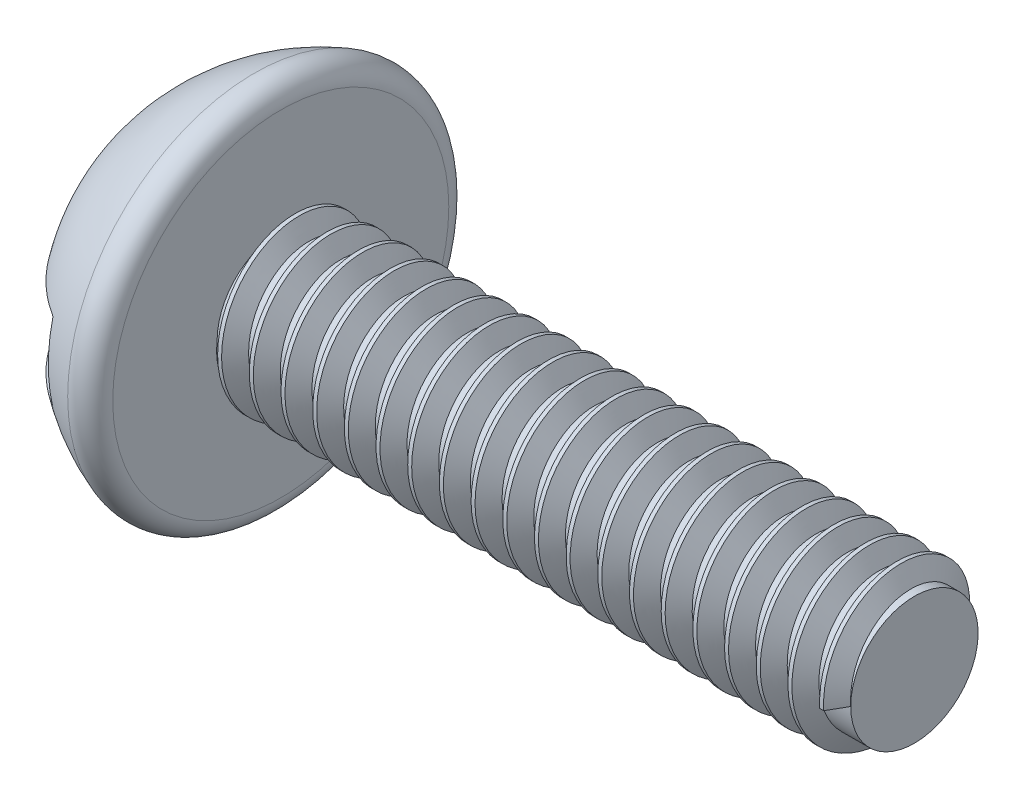
SolidWorks part; units mm, degrees
ref_plane "Front Plane" through (0, 0, 0) normal (0, 0, 1) x (1, 0, 0)
ref_plane "Top Plane" through (0, 0, 0) normal (0, 1, 0) x (1, 0, 0)
ref_plane "Right Plane" through (0, 0, 0) normal (1, 0, 0) x (0, 0, -1)
sketch "Sketch1" plane through (0, 0, 0) normal (0, 0, 1) x (1, 0, 0)
  line L0 (0, 0) -> (-6.35, 0)
  line L1 (0, 0) -> (25.4, 0)
  line L3 (0, 2.5527) -> (25.4, 2.5527)
  line L4 (25.4, 0) -> (25.4, 2.5527)
  line L5 (0, 2.5527) -> (0, 7.7771)
  arc A0 (-6.35, 0) -> (0, 7.7771) centre (1.5875, 0) cw
  dimension "D4" = 7.9375
  dimension "D1" = 25.4
  dimension "D2" = 2.5527
  dimension "D3" = 6.35
revolve "Revolve1" add sketch "Sketch1" angle 360 about L1
thread "Thread1" pitch 1.27 method extrude profile "Thread Profile1" start angle 0, offset 0, length 0, pitch 1.27, diameter 5.1054
ref_plane "Plane1" through (25.4, 0, 2.5527) normal (0, -1, 0) x (0, 0, 1)
sketch "Thread Profile1" plane through (25.4, 0, 2.5527) normal (0, -1, 0) x (0, 0, 1)
  line L0 (0, 0) -> (0, 1.27) construction
  line L1 (0, 0) -> (0.6874, 0.3969)
  line L2 (0.6874, 0.3969) -> (0.6874, 0.5556)
  line L3 (0.6874, 0.5556) -> (0, 0.9525)
  line L4 (0.6874, 0.4762) -> (0, 0.4762) construction
  line L11 (0, 0) -> (0, 0.9525)
  point P2 (0, 0)
  dimension "Pitch" = 1.27
  dimension "Profile_Angle" = 60
  dimension "Profile_Land" = 0.1588
  dimension "Profile_Height" = 0.6874
ref_plane "Plane2" through (-2.54, 0, 0) normal (1, 0, 0) x (0, 0, -1)
sketch "Sketch6" plane through (-2.54, 0, 0) normal (1, 0, 0) x (0, 0, -1)
  line L1 (12.7, 1.5875) -> (-12.7, 1.5875)
  line L2 (12.7, 1.5875) -> (12.7, -1.5875)
  line L3 (12.7, -1.5875) -> (-12.7, -1.5875)
  line L4 (-12.7, 1.5875) -> (-12.7, -1.5875)
  line L5 (1.5875, 1.5875) -> (-1.5875, 1.5875)
  line L6 (1.5875, 1.5875) -> (1.5875, 4.7625)
  line L7 (1.5875, 4.7625) -> (-1.5875, 4.7625)
  line L8 (-1.5875, 1.5875) -> (-1.5875, 4.7625)
  line L9 (1.5875, -1.5875) -> (-1.5875, -1.5875)
  line L10 (1.5875, -1.5875) -> (1.5875, -4.7625)
  line L11 (1.5875, -4.7625) -> (-1.5875, -4.7625)
  line L12 (-1.5875, -1.5875) -> (-1.5875, -4.7625)
  point P4 (-12.7, 0)
  dimension "D1" = 12.7
  dimension "D2" = 25.4
  dimension "D3" = 3.175
  dimension "D4" = 1.5875
  dimension "D5" = 3.175
  dimension "D6" = 3.175
  dimension "D7" = 1.5875
  dimension "D8" = 3.175
  dimension "D9" = 3.175
  dimension "D10" = 1.5875
extrude "Cut-Extrude1" cut sketch "Sketch6" against normal through all contours L1 L4 L3 L2 | L7 L8 L5 L6 | L12 L11 L10 L9 region at (-2.54, 0, 0)
chamfer "Chamfer1" distance 2.54 angle 45 2 edges at (-2.54, -4.7625, 0) (-2.54, 4.7625, 0)
fillet "Fillet1" radius 0.7937 1 edges at (0, 0, 7.7771)
